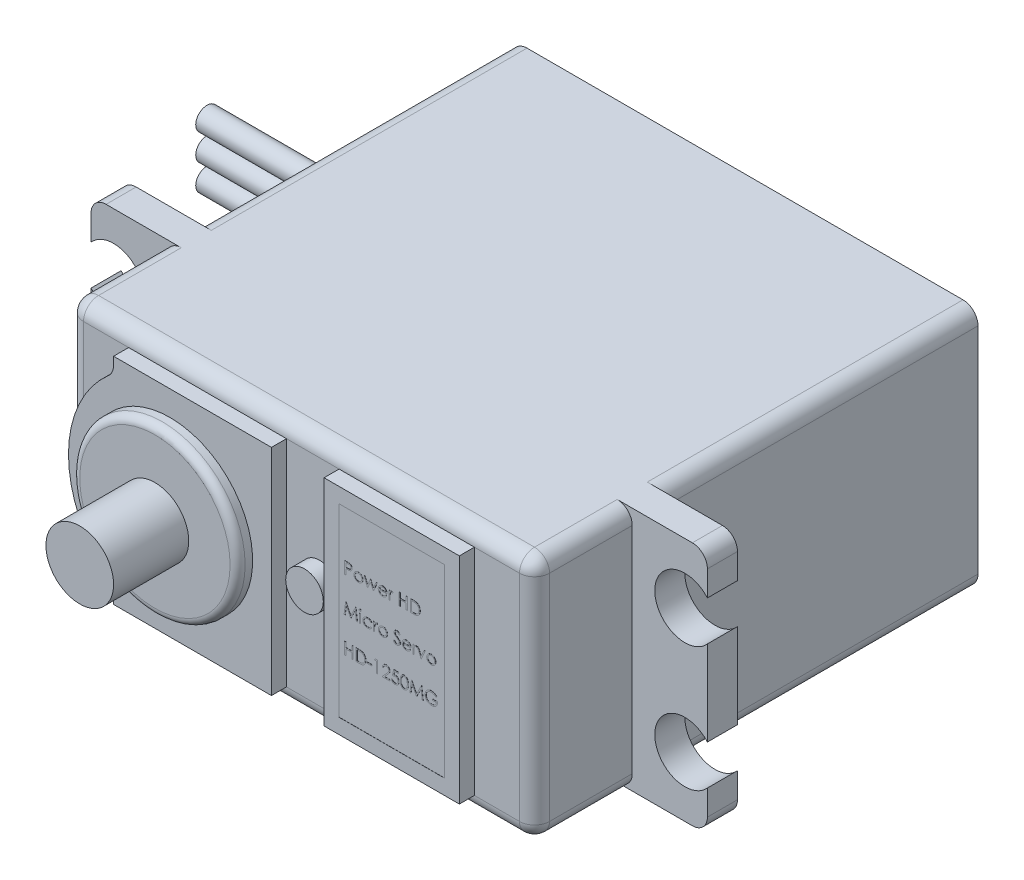
SolidWorks part; units mm, degrees
ref_plane "Ön Düzlem" through (0, 0, 0) normal (0, 0, 1) x (1, 0, 0)
ref_plane "Üst Düzlem" through (0, 0, 0) normal (0, 1, 0) x (1, 0, 0)
ref_plane "Sağ Düzlem" through (0, 0, 0) normal (1, 0, 0) x (0, 0, -1)
sketch "Çizim1" plane through (0, 0, 0) normal (0, 0, 1) x (1, 0, 0)
  line L1 (0, 0) -> (31, 0)
  line L2 (0, 0) -> (0, 16.3)
  line L3 (0, 16.3) -> (31, 16.3)
  line L4 (31, 0) -> (31, 16.3)
  dimension "D1" = 31
  dimension "D2" = 16.3
extrude "Yükseklik-Ekstrüzyon1" add sketch "Çizim1" along normal blind 29.5
sketch "Çizim3" plane through (31, 0, 0) normal (1, 0, 0) x (0, 0, -1)
  line L0 (0, 0) -> (0, 16.3) construction
  line L1 (-23, 16.3) -> (-21, 16.3)
  line L2 (-23, 16.3) -> (-23, 0)
  line L3 (-23, 0) -> (-21, 0)
  line L4 (-21, 16.3) -> (-21, 0)
  line L5 (-29.5, 16.3) -> (0, 16.3) construction
  line L6 (-29.5, 0) -> (0, 0) construction
  dimension "D1" = 21
  dimension "D2" = 2
extrude "Yükseklik-Ekstrüzyon3" add sketch "Çizim3" against normal blind 41 from offset 5
sketch "Çizim4" plane through (0, 0, 23) normal (0, 0, 1) x (1, 0, 0)
  line L0 (-5, 0) -> (0, 0) construction
  line L1 (-5, 16.3) -> (0, 16.3) construction
  line L2 (0, 16.3) -> (0, 0) construction
  line L3 (31, 0) -> (31, 16.3) construction
  circle A0 centre (-3.5, 4) radius 2
  circle A1 centre (-3.5, 12.3) radius 2
  circle A2 centre (34.5, 12.3) radius 2
  circle A3 centre (34.5, 4) radius 2
  dimension "D1" = 4
  dimension "D4" = 3.5
  dimension "D2" = 4
  dimension "D3" = 4
  dimension "D5" = 3.5
extrude "Kes-Ekstrüzyon3" cut sketch "Çizim4" against normal blind 4
sketch "Çizim5" plane through (0, 0, 0) normal (0, 0, -1) x (-1, 0, 0)
  line L0 (-31, 16.3) -> (0, 16.3) construction
  line L1 (-31, 0) -> (-31, 16.3) construction
  circle A0 centre (-15.5, 8.15) radius 1
  dimension "D3" = 2
  dimension "D1" = 8.15
  dimension "D2" = 15.5
extrude "Kes-Ekstrüzyon4" cut sketch "Çizim5" against normal blind 1
fillet "Radyus1" radius 1 16 edges at (15.5, 16.3, 29.5) (31, 8.15, 29.5) (15.5, 0, 29.5) (0, 8.15, 29.5) (0, 16.3, 26.25) (31, 16.3, 26.25) (31, 0, 26.25) (0, 0, 26.25) (0, 0, 10.5) (0, 16.3, 10.5) (31, 16.3, 10.5) (31, 0, 10.5) (-5, 16.3, 22) (36, 16.3, 22) (36, 0, 22) (-5, 0, 22)
sketch "Çizim6" plane through (0, 0, 29.5) normal (0, 0, 1) x (1, 0, 0)
  line L0 (30, 15.3) -> (1, 15.3) construction
  line L1 (18, 15.3) -> (27, 15.3)
  line L2 (18, 15.3) -> (18, 1)
  line L3 (18, 1) -> (27, 1)
  line L4 (27, 15.3) -> (27, 1)
  line L5 (1, 1) -> (30, 1) construction
  line L6 (31, 15.3) -> (31, 1) construction
  line L8 (4, 15.3) -> (14.5, 15.3)
  line L9 (4, 15.3) -> (4, 14.7699)
  line L10 (4, 1) -> (14.5, 1)
  line L11 (14.5, 15.3) -> (14.5, 1)
  line L13 (4, 1) -> (4, 1.5301)
  line L14 (1, 15.3) -> (1, 1) construction
  circle A0 centre (16.7, 8.15) radius 1.25
  arc A1 (3.6592, 2.2821) -> (3.6592, 14.0179) centre (8.8037, 8.15) cw
  arc A2 (4, 1.5301) -> (3.6592, 2.2821) centre (3, 1.5301) ccw
  arc A3 (4, 14.7699) -> (3.6592, 14.0179) centre (3, 14.7699) cw
  point P24 (4, 2)
  point P27 (4, 14.3)
  dimension "D3" = 2.5
  dimension "D7" = 10.5
  dimension "D10" = 1
  dimension "D1" = 9
  dimension "D2" = 4
  dimension "D4" = 7.15
  dimension "D5" = 10.5
  dimension "D6" = 3
  dimension "D8" = 1
  dimension "D9" = 1
  dimension "D11" = 1.3
extrude "Yükseklik-Ekstrüzyon5" add sketch "Çizim6" along normal blind 1
sketch "Çizim8" plane through (0, 0, 30.5) normal (0, 0, 1) x (1, 0, 0)
  line L0 (27, 15.3) -> (18, 15.3) construction
  line L1 (19, 14.3) -> (26, 14.3)
  line L2 (19, 14.3) -> (19, 2)
  line L3 (19, 2) -> (26, 2)
  line L4 (26, 14.3) -> (26, 2)
  line L5 (18, 15.3) -> (18, 1) construction
  line L6 (27, 1) -> (27, 15.3) construction
  line L7 (18, 1) -> (27, 1) construction
  dimension "D1" = 1
  dimension "D2" = 1
  dimension "D3" = 1
  dimension "D4" = 1
extrude "Kes-Ekstrüzyon5" cut sketch "Çizim8" against normal blind 0.01
sketch "Çizim9" plane through (0, 0, 30.49) normal (0, 0, 1) x (1, 0, 0)
  text T0 "Power HD\r\nMicro Servo\r\nHD-1250MG" font "Century Gothic" height in points 3
extrude "Yükseklik-Ekstrüzyon7" add sketch "Çizim9" along normal blind 0.01
sketch "Çizim10" plane through (0, 0, 30.5) normal (0, 0, 1) x (1, 0, 0)
  line L0 (14.5, 15.3) -> (4, 15.3) construction
  circle A0 centre (7.75, 8.15) radius 5.5
  dimension "D1" = 11
  dimension "D2" = 7.15
  dimension "D3" = 6.75
extrude "Yükseklik-Ekstrüzyon8" add sketch "Çizim10" along normal blind 1
fillet "Radyus2" radius 0.5 1 edges at (13.25, 8.15, 31.5)
sketch "Çizim11" plane through (0, 0, 31.5) normal (0, 0, 1) x (1, 0, 0)
  circle A0 centre (7.75, 8.15) radius 2.25
  circle A1 centre (7.75, 8.15) radius 5 construction
  dimension "D1" = 4.5
extrude "Yükseklik-Ekstrüzyon9" add sketch "Çizim11" along normal blind 5
sketch "Çizim12" plane through (0, 0, 0) normal (0, -1, 0) x (1, 0, 0)
  text T0 "Power HD\r\nMicro Servo\r\nHD-1250MG" font "Century Gothic" height in points 12
extrude "Yükseklik-Ekstrüzyon10" add sketch "Çizim12" along normal blind 0.01
sketch "Çizim14" plane through (0, 0, 0) normal (-1, 0, 0) x (0, 0, 1)
  line L0 (0, 16.3) -> (21, 16.3) construction
  line L1 (7, 11.3) -> (10, 11.3)
  line L2 (7, 11.3) -> (7, 5)
  line L3 (7, 5) -> (10, 5)
  line L4 (10, 11.3) -> (10, 5)
  line L5 (0, 15.3) -> (0, 1) construction
  dimension "D1" = 6.3
  dimension "D2" = 5
  dimension "D3" = 7
  dimension "D4" = 3
extrude "Yükseklik-Ekstrüzyon12" add sketch "Çizim14" along normal blind 1
sketch "Çizim15" plane through (-1, 0, 0) normal (-1, 0, 0) x (0, 0, 1)
  line L0 (10, 11.3) -> (7, 11.3) construction
  circle A0 centre (8.2861, 9.9) radius 0.75
  circle A1 centre (8.2861, 8.15) radius 0.75
  circle A2 centre (8.2861, 6.4) radius 0.75
  dimension "D1" = 1.5
  dimension "D2" = 1.75
  dimension "D3" = 1.75
  dimension "D4" = 1.4
extrude "Yükseklik-Ekstrüzyon13" add sketch "Çizim15" along normal blind 11
